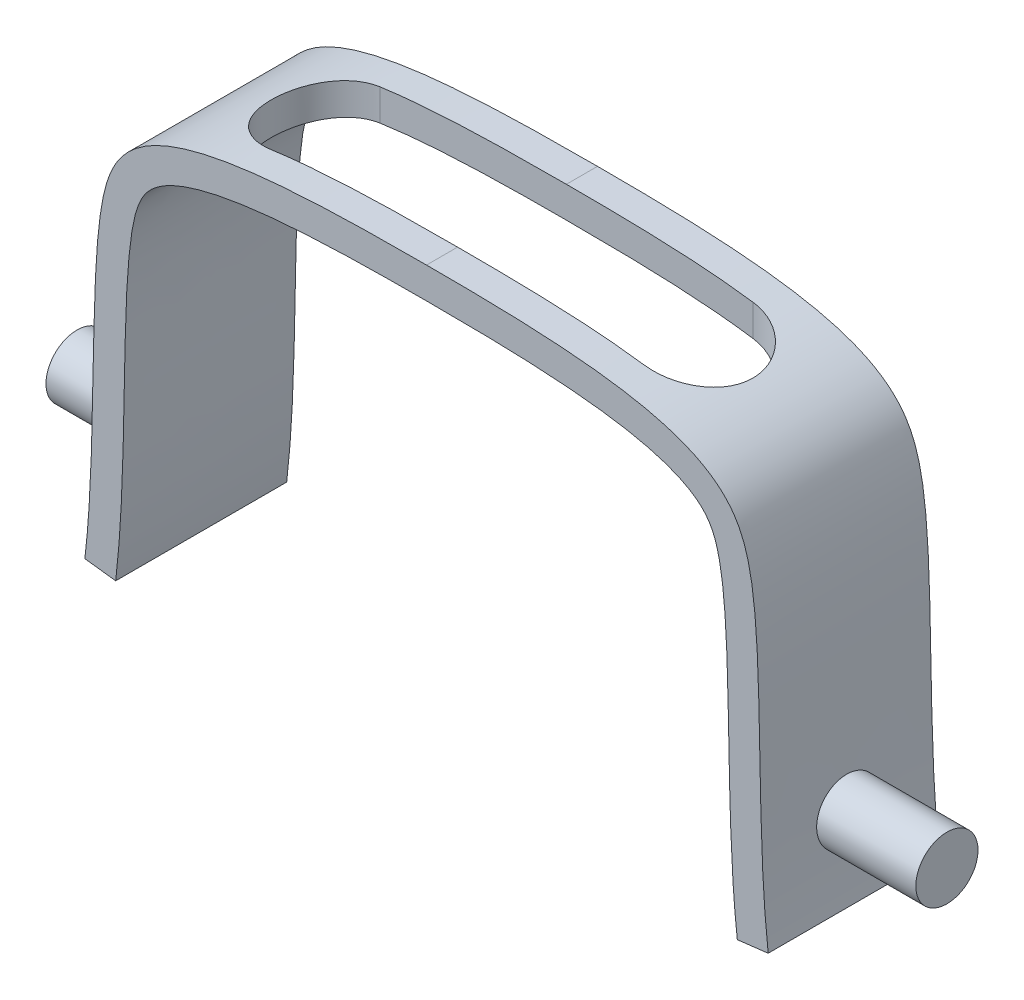
SolidWorks part; units mm, degrees
ref_plane "Front Plane" through (0, 0, 0) normal (0, 0, 1) x (1, 0, 0)
ref_plane "Top Plane" through (0, 0, 0) normal (0, 1, 0) x (1, 0, 0)
ref_plane "Right Plane" through (0, 0, 0) normal (1, 0, 0) x (0, 0, -1)
sketch "Sketch3" plane through (0, 0, 0) normal (0, 0, 1) x (1, 0, 0)
  line L0 (-27.9169, 0.8181) -> (-25.3947, 0.5178)
  line L1 (0, 0) -> (0, 49.1985) construction
  line L2 (25.3947, 0.5178) -> (27.9169, 0.8181)
  spline S0 degree 3 poles (-25.3947, 0.5178) (-24.2897, 9.8003) (-25.3092, 25.1441) (-21.1033, 32.6724) (-9.2595, 33.02) (0, 33.02) knots 0 0 0 0 0.433889 0.533889 1 1 1 1
  spline S1 degree 1 poles (-27.9169, 0.8181) (0, 35.56) knots 0 0 1 1 construction
  spline S2 degree 3 poles (25.3947, 0.5178) (24.2897, 9.8003) (25.3092, 25.1441) (21.1033, 32.6724) (9.2595, 33.02) (0, 33.02) knots 0 0 0 0 0.433889 0.533889 1 1 1 1
  spline S3 degree 1 poles (27.9169, 0.8181) (0, 35.56) knots 0 0 1 1 construction
  spline S4 degree 3 poles (-27.9169, 0.8181) (-27.8388, 1.4744) (-27.7079, 2.7671) (-27.5019, 5.5401) (-27.3469, 9.1496) (-27.2514, 13.5493) (-27.1763, 17.8126) (-27.0466, 21.7627) (-26.8281, 24.6584) (-26.5322, 26.6944) (-26.226, 28.0843) (-25.7782, 29.3834) (-25.0846, 30.615) (-24.1369, 31.6618) (-22.6857, 32.7428) (-20.6204, 33.6849) (-17.7897, 34.4469) (-13.5692, 35.129) (-7.5883, 35.5185) (-2.5048, 35.56) (0, 35.56) knots 0 0 0 0 0.03125 0.0625 0.125 0.1875 0.25 0.3125 0.375 0.40625 0.4375 0.46875 0.5 0.53125 0.5625 0.625 0.6875 0.75 0.875 1 1 1 1
  spline S5 degree 3 poles (0, 35.56) (2.5048, 35.56) (7.5883, 35.5185) (13.5692, 35.129) (17.7897, 34.4469) (20.6204, 33.6849) (22.6857, 32.7428) (24.1369, 31.6618) (25.0846, 30.615) (25.7782, 29.3834) (26.226, 28.0843) (26.5322, 26.6944) (26.8281, 24.6584) (27.0466, 21.7627) (27.1763, 17.8126) (27.2514, 13.5493) (27.3469, 9.1496) (27.5019, 5.5401) (27.7079, 2.7671) (27.8388, 1.4744) (27.9169, 0.8181) knots 0 0 0 0 0.125 0.25 0.3125 0.375 0.4375 0.46875 0.5 0.53125 0.5625 0.59375 0.625 0.6875 0.75 0.8125 0.875 0.9375 0.96875 1 1 1 1
  dimension "D1" = 25.4
  dimension "D2" = 33.02
  dimension "D3" = 2.54
extrude "main body" add sketch "Sketch3" along normal mid plane 13.97
ref_plane "top of rounded bit" through (0, 35.56, 0) normal (0, 1, 0) x (1, 0, 0)
sketch "Sketch4" plane through (0, 35.56, 0) normal (0, 1, 0) x (1, 0, 0)
  line L0 (-15.24, 0) -> (15.24, 0) construction
  line L1 (0, -6.985) -> (0, 6.985) construction
  line L2 (-15.24, 4.445) -> (15.24, 4.445)
  line L3 (-15.24, -4.445) -> (15.24, -4.445)
  arc A0 (-15.24, 4.445) -> (-15.24, -4.445) centre (-15.24, 0) ccw
  arc A1 (15.24, -4.445) -> (15.24, 4.445) centre (15.24, 0) ccw
  point P4 (0, 0)
  dimension "D1" = 8.89
  dimension "D2" = 30.48
extrude "slot for joystick" cut sketch "Sketch4" against normal blind 127 and the other way blind 127
ref_plane "nibble plane one" through (-27.9169, 0, 0) normal (1, 0, 0) x (0, 0, -1)
ref_plane "nibble plane two" through (27.9169, 0, 0) normal (1, 0, 0) x (0, 0, -1)
sketch "Sketch5" plane through (27.9169, 0, 0) normal (1, 0, 0) x (0, 0, -1)
  line L0 (-6.985, 0.8181) -> (6.985, 0.8181) construction
  circle A0 centre (0, 7.1681) radius 2.54
  point P2 (0, 0.8181)
  dimension "D1" = 6.35
extrude "nibble two" add sketch "Sketch5" along normal blind 7.62 and the other way up to body
sketch "Sketch6" plane through (-27.9169, 0, 0) normal (1, 0, 0) x (0, 0, -1)
  line L0 (-6.985, 0.8181) -> (6.985, 0.8181) construction
  circle A0 centre (0, 7.1681) radius 2.54
  point P2 (0, 0.8181)
  dimension "D1" = 6.35
extrude "nibble one" add sketch "Sketch6" against normal blind 7.62 and the other way up to body
ref_point "nibble center"
ref_plane "nibble flag plane" through (0, 7.1681, 0) normal (0, 1, 0) x (1, 0, 0)
sketch "Sketch7" plane through (0, 7.1681, 0) normal (0, 1, 0) x (1, 0, 0)
  line L1 (-31.3343, 0.6195) -> (-27.5243, 0.6195)
  line L2 (-31.3343, 0.6195) -> (-31.3343, -0.6505)
  line L3 (-31.3343, -0.6505) -> (-27.5243, -0.6505)
  line L4 (-27.5243, 0.6195) -> (-27.5243, -0.6505)
  line L5 (-31.3343, 0.6195) -> (-27.5243, -0.6505) construction
  line L6 (-31.3343, -0.6505) -> (-27.5243, 0.6195) construction
  point P0 (-29.4293, -0.0155)
  dimension "D1" = 1.27
  dimension "D2" = 3.81
extrude "flag" add sketch "Sketch7" against normal blind 0.254
